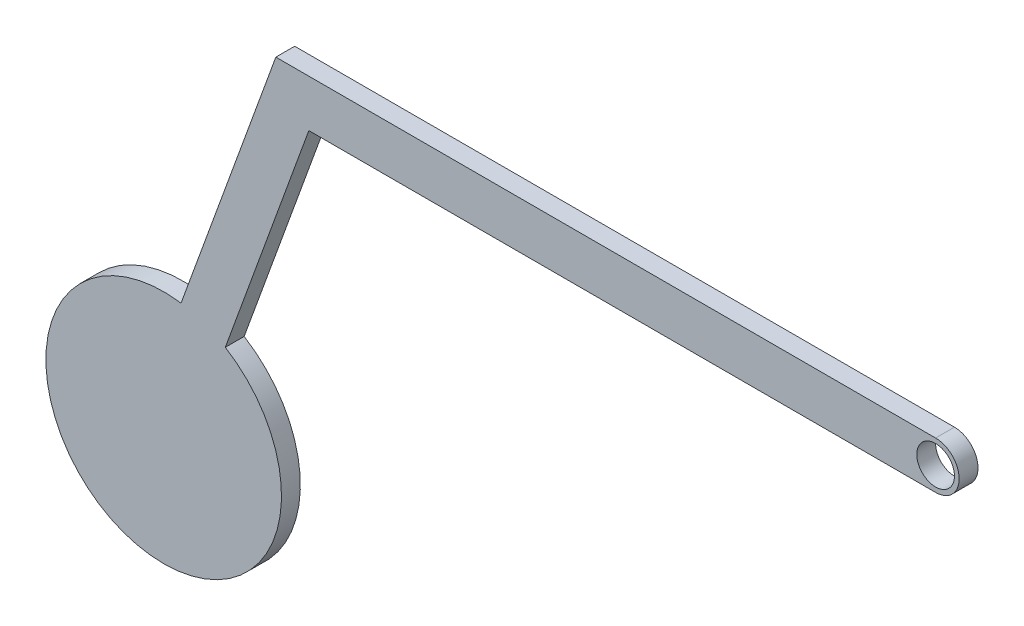
SolidWorks part; units mm, degrees
ref_plane "Front Plane" through (0, 0, 0) normal (0, 0, 1) x (1, 0, 0)
ref_plane "Top Plane" through (0, 0, 0) normal (0, 1, 0) x (1, 0, 0)
ref_plane "Right Plane" through (0, 0, 0) normal (1, 0, 0) x (0, 0, -1)
ref_axis "X" through (-88.99, 0, 0) along (1, 0, 0)
ref_axis "Y" through (0, 55, 0) along (0, -1, 0)
ref_axis "Z" through (0, 0, -88.99) along (0, 0, 1)
sketch "Sketch1" plane through (0, 0, 0) normal (0, 0, 1) x (1, 0, 0)
  line L0 (9.5035, 33.4202) -> (11.8984, 40)
  line L1 (1.8396, 12.3639) -> (9.5035, 33.4202)
  line L2 (18.9005, 40) -> (81.8984, 40)
  line L4 (22.3624, 35) -> (81.8984, 35)
  line L5 (11.8984, 40) -> (18.9005, 40)
  line L6 (81.8984, 35) -> (81.8984, 40) construction
  line L7 (2.3492, -0.855) -> (15.3994, 35) construction
  line L8 (15.3994, 35) -> (81.8984, 35) construction
  line L9 (-2.3492, 0.8551) -> (11.8984, 40) construction
  line L10 (11.8984, 40) -> (81.8984, 40) construction
  line L11 (6.5381, 10.6538) -> (13.2928, 29.212)
  line L12 (12.5, 0) -> (84.8669, 0) construction
  line L13 (22.3624, 35) -> (15.3994, 35)
  line L14 (15.3994, 35) -> (13.2928, 29.212)
  arc A1 (81.8984, 35) -> (81.8984, 40) centre (81.8984, 37.5) ccw
  arc A4 (1.8396, 12.3639) -> (6.5381, 10.6538) centre (0, 0) ccw
  circle A6 centre (81.8984, 37.5) radius 2
  point P10 (81.8984, 40)
  point P17 (11.8984, 40)
  dimension "D5" = 35
  dimension "D6" = 25
  dimension "D1" = 4
  dimension "D2" = 5
  dimension "D3" = 70
  dimension "D4" = 5
extrude "Boss-Extrude1" add sketch "Sketch1" along normal blind 2 contours L2 A1 L4 L13 L14 L11 A4 L1 L0 L5
sketch "Sketch4" plane through (0, 0, 2) normal (0, 0, 1) x (1, 0, 0)
  circle A0 centre (81.8984, 37.5) radius 2
  dimension "D1" = 4
extrude "Cut-Extrude1" cut sketch "Sketch4" against normal blind 5
